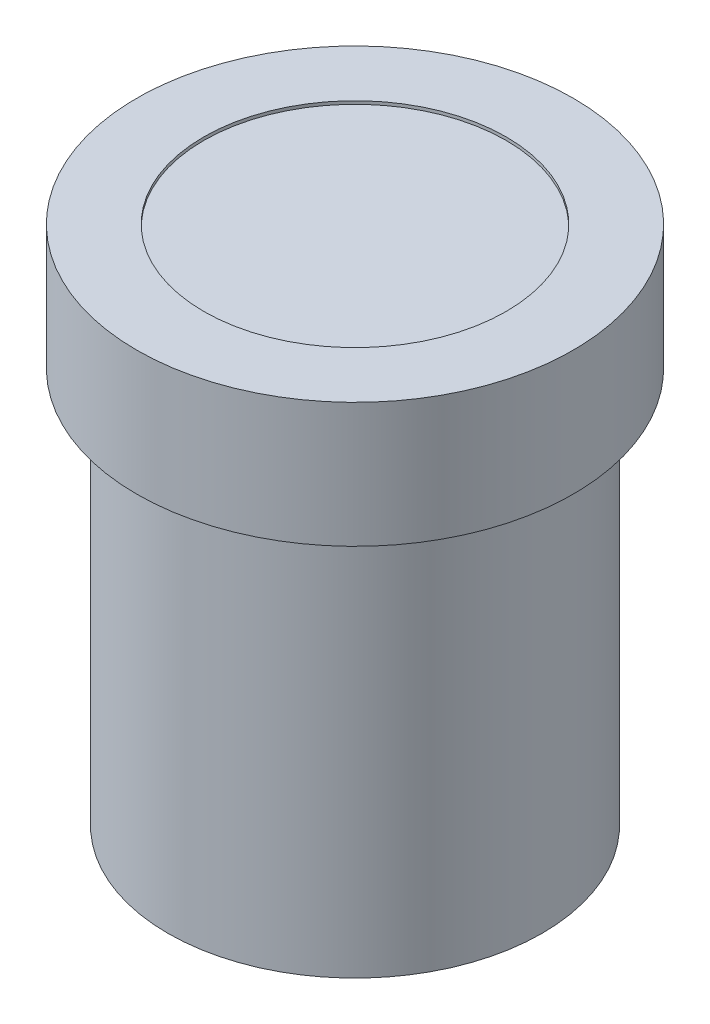
SolidWorks part; units mm, degrees
ref_plane "Спереди" through (0, 0, 0) normal (0, 0, 1) x (1, 0, 0)
ref_plane "Сверху" through (0, 0, 0) normal (0, 1, 0) x (1, 0, 0)
ref_plane "Справа" through (0, 0, 0) normal (1, 0, 0) x (0, 0, -1)
sketch "Sketch1" plane through (0, 0, 0) normal (0, 1, 0) x (1, 0, 0)
  circle A0 centre (0, 0) radius 2.25
  circle A1 centre (0, 0) radius 6
  dimension "D1" = 12
  dimension "D2" = 4.5
extrude "Boss-Extrude1" add sketch "Sketch1" along normal blind 12.7
sketch "Sketch2" plane through (0, 12.7, 0) normal (0, 1, 0) x (1, 0, 0)
  circle A0 centre (0, 0) radius 7
  circle A1 centre (0, 0) radius 4.85
  circle A2 centre (0, 0) radius 2.25 construction
  circle A3 centre (0, 0) radius 2.25
  circle M1 centre (0, 0) radius 6
  dimension "D1" = 14
  dimension "D2" = 9.7
extrude "Boss-Extrude2" add sketch "Sketch2" along normal blind 4 contours A0 M1 | A1 M1 region at (-6.802, 12.7, 0) region at (-5.8303, 12.7, 0)
extrude "Boss-Extrude3" add sketch "Sketch2<2>" against normal blind 0.1 from offset 3.9 contours A1
sketch "Sketch2<2>" plane through (0, 12.7, 0) normal (0, 1, 0) x (1, 0, 0) same geometry as "Sketch2"
